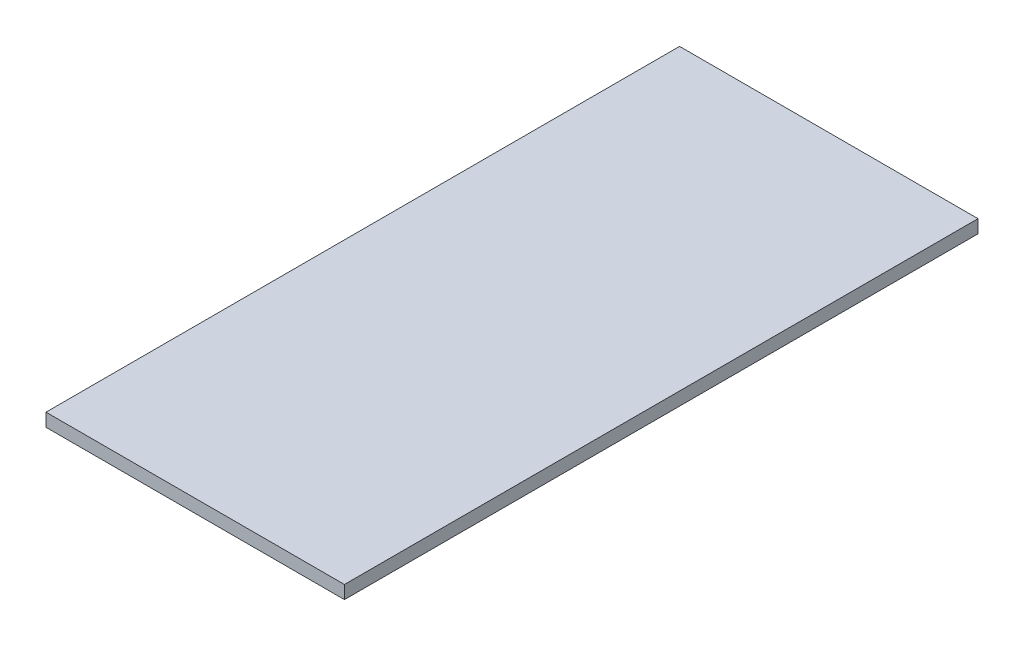
SolidWorks part; units mm, degrees
ref_plane "Front Plane" through (0, 0, 0) normal (0, 0, 1) x (1, 0, 0)
ref_plane "Top Plane" through (0, 0, 0) normal (0, 1, 0) x (1, 0, 0)
ref_plane "Right Plane" through (0, 0, 0) normal (1, 0, 0) x (0, 0, -1)
sketch "Sketch1" plane through (0, 0, 0) normal (0, 1, 0) x (1, 0, 0)
  line L1 (80.8254, -230.0534) -> (-78.1754, -230.0534)
  line L2 (80.8254, -230.0534) -> (80.8254, 107.5009)
  line L3 (80.8254, 107.5009) -> (-78.1754, 107.5009)
  line L4 (-78.1754, -230.0534) -> (-78.1754, 107.5009)
  line L5 (80.8254, -230.0534) -> (-78.1754, 107.5009) construction
  line L6 (80.8254, 107.5009) -> (-78.1754, -230.0534) construction
  point P1 (0, 0)
  point P6 (79.7654, 107.5009)
  point P8 (79.7654, -281.1127)
  point P9 (79.7654, -230.0534)
  point P10 (0, 0)
  point P11 (-79.2354, 107.5009)
extrude "Boss-Extrude1" add sketch "Sketch1" along normal blind 7
